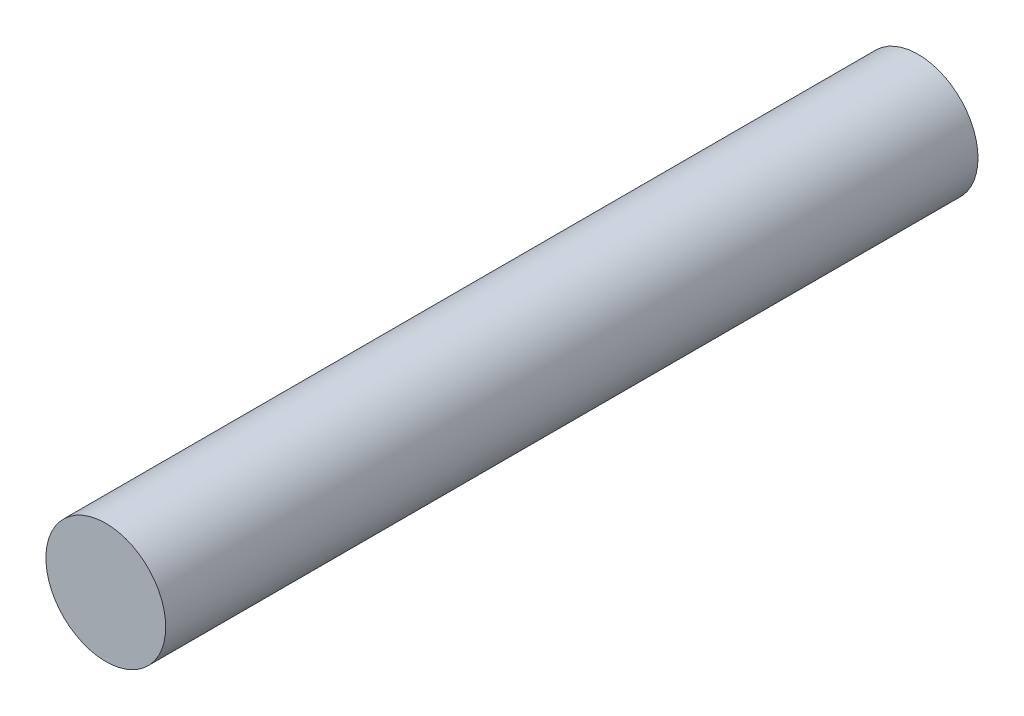
SolidWorks part; units mm, degrees
ref_plane "Front Plane" through (0, 0, 0) normal (0, 0, 1) x (1, 0, 0)
ref_plane "Top Plane" through (0, 0, 0) normal (0, 1, 0) x (1, 0, 0)
ref_plane "Right Plane" through (0, 0, 0) normal (1, 0, 0) x (0, 0, -1)
sketch "Sketch1" plane through (0, 0, 0) normal (0, 0, 1) x (1, 0, 0)
  circle A0 centre (0, 0) radius 1.475
  dimension "D1" = 2.95
extrude "Boss-Extrude1" add sketch "Sketch1" along normal blind 10 and the other way blind 10
